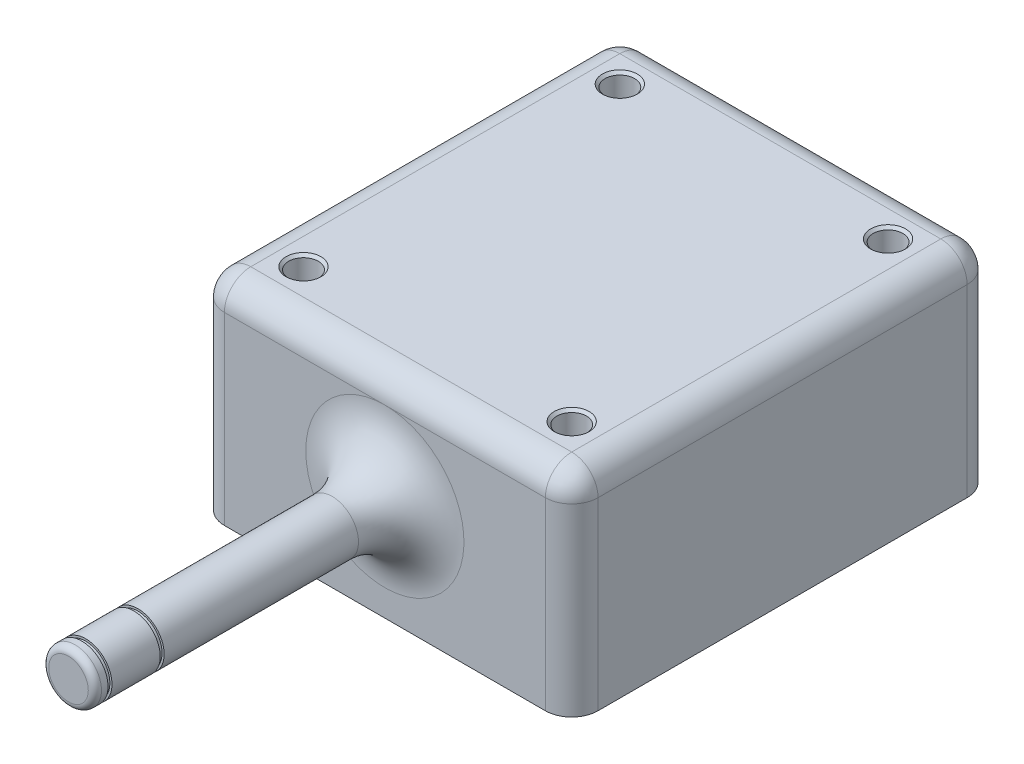
SolidWorks part; units mm, degrees
ref_plane "Front Plane" through (0, 0, 0) normal (0, 0, 1) x (1, 0, 0)
ref_plane "Top Plane" through (0, 0, 0) normal (0, 1, 0) x (1, 0, 0)
ref_plane "Right Plane" through (0, 0, 0) normal (1, 0, 0) x (0, 0, -1)
sketch "Sketch1" plane through (0, 0, 0) normal (0, 0, 1) x (1, 0, 0)
  line L1 (-45, 25.4) -> (45, 25.4)
  line L2 (-45, 25.4) -> (-45, -25.4)
  line L3 (-45, -25.4) -> (45, -25.4)
  line L4 (45, 25.4) -> (45, -25.4)
  line L5 (-45, 25.4) -> (45, -25.4) construction
  line L6 (-45, -25.4) -> (45, 25.4) construction
  circle A0 centre (0, 0) radius 6.35
  point P0 (0, 0)
  dimension "D1" = 12.7
  dimension "D2" = 90
  dimension "D3" = 50.8
extrude "Boss-Extrude1" add sketch "Sketch1" against normal blind 101.6 contours L2 L3 L4 L1
sketch "Sketch10" plane through (0, 0, 0) normal (0, 0, 1) x (1, 0, 0)
  line L0 (-45, -25.4) -> (45, -25.4) construction
  line L1 (-101.6, -25.4) -> (101.6, -25.4)
  line L2 (-101.6, -25.4) -> (-101.6, -228.6)
  line L3 (-101.6, -228.6) -> (101.6, -228.6)
  line L4 (101.6, -25.4) -> (101.6, -228.6)
  point P6 (0, -25.4)
  point P7 (0, -25.4)
  dimension "D1" = 203.2
extrude "Boss-Extrude2" add sketch "Sketch1<3>" along normal blind 76.2 contours A0 region at (0, 0, 0)
sketch "Sketch1<3>" plane through (0, 0, 0) normal (0, 0, 1) x (1, 0, 0) same geometry as "Sketch1"
fillet "Fillet1" radius 6.35 8 edges at (45, 0, 0) (45, 0, -101.6) (-45, 0, -101.6) (-45, 0, 0) (0, 25.4, -101.6) (45, 25.4, -50.8) (0, 25.4, 0) (-45, 25.4, -50.8)
fillet "Fillet2" radius 12.7 1 edges at (6.35, 0, 0)
sketch "Sketch2" plane through (0, 25.4, 0) normal (0, 1, 0) x (1, 0, 0)
  line L0 (-38.65, 50.8) -> (0, 50.8) construction
  line L1 (-32.3, 88.9) -> (32.3, 88.9)
  line L2 (-32.3, 88.9) -> (-32.3, 12.7)
  line L3 (-32.3, 12.7) -> (32.3, 12.7)
  line L4 (32.3, 88.9) -> (32.3, 12.7)
  line L5 (-32.3, 88.9) -> (32.3, 12.7) construction
  line L6 (-32.3, 12.7) -> (32.3, 88.9) construction
  line L7 (-38.65, 95.25) -> (-38.65, 6.35) construction
  line L8 (0, 50.8) -> (0, 6.35) construction
  line L9 (-38.65, 6.35) -> (38.65, 6.35) construction
  line L10 (-32.3, 88.9) -> (-32.3, 95.25) construction
  line L11 (38.65, 95.25) -> (-38.65, 95.25) construction
  line L12 (-32.3, 88.9) -> (-38.65, 88.9) construction
  circle A0 centre (-32.3, 88.9) radius 3.175
  point P0 (0, 50.8)
  dimension "D1" = 6.35
  dimension "D2" = 3.175
hole_wizard "1/4 Clearance Hole1" positions "Sketch3" profile "Sketch4" hole size "1/4" standard "ANSI Inch" end condition through all
sketch "Sketch3" plane through (0, 25.4, 0) normal (0, 1, 0) x (1, 0, 0)
  point P0 (-32.3, 88.9)
  point P3 (-32.3, 12.7)
  point P6 (32.3, 12.7)
  point P9 (32.3, 88.9)
sketch "Sketch4" plane through (-32.3, 25.4, -88.9) normal (1, 0, 0) x (0, 0, 1)
  line L0 (0, 0) -> (0, 50.8)
  line L1 (0, 50.8) -> (3.5687, 50.8)
  line L2 (3.5687, 50.8) -> (3.5687, 0.635)
  line L3 (3.5687, 0.635) -> (4.2037, 0)
  line L5 (4.2037, 0) -> (0, 0)
  line L6 (-3.5687, 0.635) -> (-4.2037, 0) construction
  line L11 (0, -6.35) -> (0, 107.95) construction
  dimension "Thru Hole Dia." = 7.1374
  dimension "Thru Hole Depth" = 50.8
  dimension "Near C'Sink Dia." = 8.4074
  dimension "Near C'Sink Angle" = 90
ref_plane "Plane1" through (0, 6.35, 0) normal (0, 1, 0) x (1, 0, 0)
sketch "Sketch5" plane through (0, 6.35, 0) normal (0, 1, 0) x (1, 0, 0)
  line L0 (-45, -60.4625) -> (45, -60.4625)
  line L1 (-45, -72.0725) -> (45, -72.0725)
  line L2 (-45, -72.0725) -> (-45, -60.4625)
  line L3 (45, -60.4625) -> (45, -72.0725)
  line L4 (-45, -66.2675) -> (0, -66.2675) construction
  line L5 (0, -60.4625) -> (0, -72.0725) construction
  line L6 (0, -76.2) -> (0, -72.0725) construction
  line L7 (-6.35, -76.2) -> (6.35, -76.2) construction
  line L8 (-6.6675, -73.025) -> (0, -72.0725) construction
  line L9 (-6.6675, -72.0725) -> (6.6675, -72.0725)
  line L10 (-6.6675, -72.0725) -> (-6.6675, -73.025)
  line L11 (-6.6675, -73.025) -> (6.6675, -73.025)
  line L12 (6.6675, -72.0725) -> (6.6675, -73.025)
  line L13 (0, -72.0725) -> (6.6675, -73.025) construction
  line L14 (0, -60.4625) -> (6.6675, -59.51) construction
  line L15 (-6.6675, -59.51) -> (0, -60.4625) construction
  line L16 (6.6675, -60.4625) -> (6.6675, -59.51)
  line L17 (-6.6675, -59.51) -> (6.6675, -59.51)
  line L18 (-6.6675, -60.4625) -> (-6.6675, -59.51)
  line L19 (-6.6675, -60.4625) -> (6.6675, -60.4625)
  dimension "D1" = 11.61
  dimension "D2" = 90
  dimension "D3" = 0.9525
  dimension "D4" = 13.335
  dimension "D5" = 3.175
ref_plane "Plane2" through (0, 0, 72.0725) normal (0, 0, 1) x (1, 0, 0)
ref_plane "Plane3" through (0, 0, 60.4625) normal (0, 0, 1) x (1, 0, 0)
sketch "Sketch6" plane through (0, 0, 76.2) normal (0, 0, 1) x (1, 0, 0)
  circle A0 centre (0, 0) radius 5.842
  dimension "D1" = 11.684
sketch "Sketch7" plane through (0, 0, 72.0725) normal (0, 0, 1) x (1, 0, 0)
  circle A1 centre (0, 0) radius 5.842
  circle A2 centre (0, 0) radius 5.842
  circle A3 centre (0, 0) radius 6.35
  circle A4 centre (0, 0) radius 6.35
  dimension "D1" = 0
  dimension "D2" = 0
sketch "Sketch8" plane through (0, 0, 60.4625) normal (0, 0, 1) x (1, 0, 0)
  circle A1 centre (0, 0) radius 5.842
  circle A2 centre (0, 0) radius 5.842
  circle A3 centre (0, 0) radius 6.35
  circle A4 centre (0, 0) radius 6.35
  dimension "D1" = 0
  dimension "D2" = 0
extrude "Cut-Extrude1" cut sketch "Sketch7" along normal up to vertex (0.9525 mm away) contours A4 A2 region at (-6.1704, 0, 72.0725) up to point (6.6675, 6.35, 73.025)
extrude "Cut-Extrude2" cut sketch "Sketch8" against normal up to vertex (0.9525 mm away) contours A4 A2 region at (-6.1704, 0, 60.4625) up to point (-6.6675, 6.35, 59.51)
fillet "Fillet3" radius 1.5875 1 edges at (6.35, 0, 76.2)
